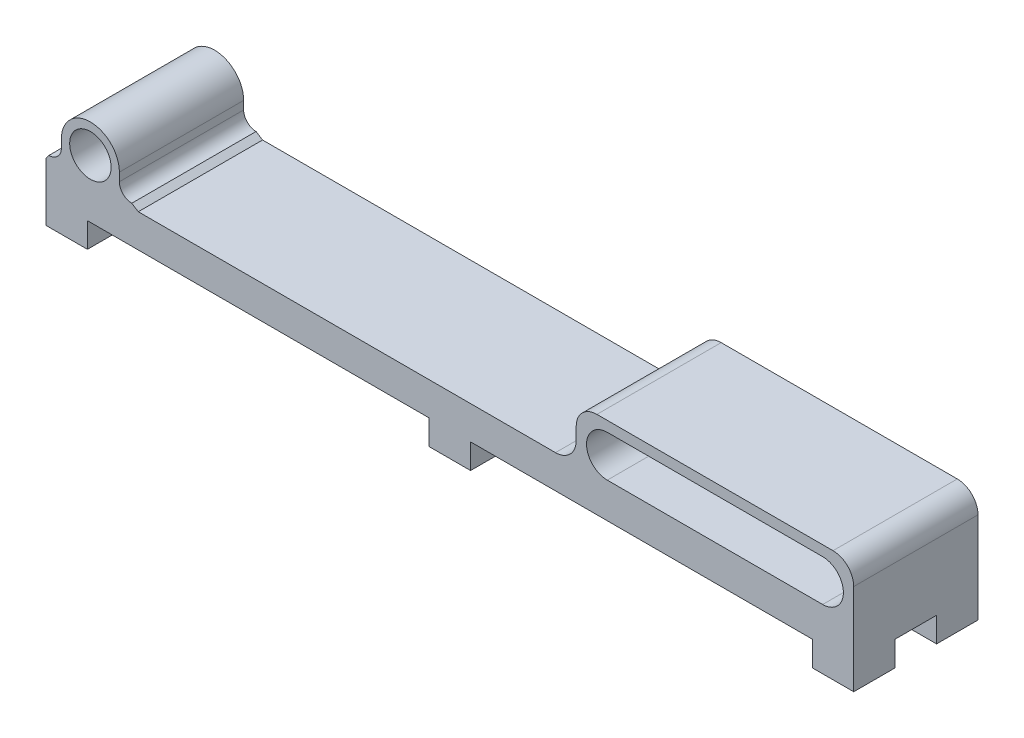
SolidWorks part; units mm, degrees
ref_plane "Front Plane" through (0, 0, 0) normal (0, 0, 1) x (1, 0, 0)
ref_plane "Top Plane" through (0, 0, 0) normal (0, 1, 0) x (1, 0, 0)
ref_plane "Right Plane" through (0, 0, 0) normal (1, 0, 0) x (0, 0, -1)
sketch "Sketch1" plane through (0, 0, 0) normal (0, 1, 0) x (1, 0, 0)
  line L1 (0, 0) -> (195, 0)
  line L2 (0, 0) -> (0, 30)
  line L3 (0, 30) -> (195, 30)
  line L4 (195, 0) -> (195, 30)
  dimension "D1" = 195
  dimension "D2" = 30
extrude "Boss-Extrude1" add sketch "Sketch1" along normal blind 8
sketch "Sketch2" plane through (0, 8, 0) normal (0, 1, 0) x (1, 0, 0)
  line L0 (195, 30) -> (0, 30) construction
  line L1 (4.7153, 30) -> (16.7153, 30)
  line L2 (4.7153, 30) -> (4.7153, 0)
  line L3 (4.7153, 0) -> (16.7153, 0)
  line L4 (16.7153, 30) -> (16.7153, 0)
  line L5 (0, 0) -> (195, 0) construction
  dimension "D1" = 12
extrude "Boss-Extrude2" add sketch "Sketch2" along normal blind 12
sketch "Sketch4" plane through (0, 0, -30) normal (0, 0, -1) x (-1, 0, 0)
  line L0 (-16.7153, 20) -> (-4.7153, 20) construction
  line L1 (-4.7153, 20) -> (-4.7153, 8) construction
  circle A0 centre (-10.7153, 14) radius 5
  dimension "D1" = 6
  dimension "D2" = 6
extrude "Cut-Extrude1" cut sketch "Sketch4" against normal through all
fillet "Fillet1" radius 4 2 edges at (4.7153, 8, -15) (16.7153, 8, -15)
fillet "Fillet2" radius 6 2 edges at (4.7153, 20, -15) (16.7153, 20, -15)
sketch "Sketch11" plane through (0, 0, -30) normal (0, 0, -1) x (-1, 0, 0)
  line L0 (-16.7153, 14) -> (-16.7153, 12) construction
  line L2 (-4.7153, 14) -> (-4.7153, 12) construction
  line L3 (-16.7153, 14) -> (-16.7153, 12)
  line L4 (-4.7153, 14) -> (-4.7153, 12)
  line L5 (-17.7153, 14) -> (-17.7153, 12)
  line L6 (-3.7153, 14) -> (-3.7153, 12)
  line L7 (-20.7153, 9) -> (-22.2788, 8)
  line L8 (-20.7153, 8) -> (-195, 8) construction
  line L9 (-22.2788, 8) -> (-20.7153, 8)
  line L10 (-0.7153, 9) -> (0, 8)
  line L11 (0, 8) -> (-0.7153, 8)
  arc A4 (-4.7153, 14) -> (-10.7153, 20) centre (-10.7153, 14) ccw construction
  arc A5 (-10.7153, 20) -> (-16.7153, 14) centre (-10.7153, 14) ccw construction
  arc A6 (-20.7153, 8) -> (-16.7153, 12) centre (-20.7153, 12) ccw construction
  arc A7 (-4.7153, 12) -> (-0.7153, 8) centre (-0.7153, 12) ccw construction
  arc A8 (-20.7153, 8) -> (-16.7153, 12) centre (-20.7153, 12) ccw
  arc A9 (-4.7153, 12) -> (-0.7153, 8) centre (-0.7153, 12) ccw
  arc A10 (-4.7153, 14) -> (-10.7153, 20) centre (-10.7153, 14) ccw
  arc A11 (-10.7153, 20) -> (-16.7153, 14) centre (-10.7153, 14) ccw
  arc A12 (-20.7153, 9) -> (-17.7153, 12) centre (-20.7153, 12) ccw
  arc A13 (-10.7153, 21) -> (-17.7153, 14) centre (-10.7153, 14) ccw
  arc A14 (-3.7153, 14) -> (-10.7153, 21) centre (-10.7153, 14) ccw
  arc A15 (-3.7153, 12) -> (-0.7153, 9) centre (-0.7153, 12) ccw
  dimension "D1" = 1
extrude "Boss-Extrude4" add sketch "Sketch11" against normal up to surface (30 mm away) up to face at (5.7153, 14, 0)
sketch "Sketch15" plane through (0, 8, 0) normal (0, 1, 0) x (1, 0, 0)
  line L0 (195, 15) -> (22.2788, 15) construction
  line L1 (195, 30) -> (128, 30)
  line L2 (195, 30) -> (195, 23)
  line L3 (195, 23) -> (128, 23)
  line L4 (128, 30) -> (128, 23)
  line L5 (195, 0) -> (195, 30) construction
  line L6 (22.2788, 0) -> (22.2788, 30) construction
  line L7 (195, 7) -> (128, 7)
  line L8 (128, 0) -> (128, 7)
  line L9 (195, 0) -> (128, 0)
  line L10 (195, 0) -> (195, 7)
  dimension "D1" = 7
  dimension "D2" = 67
extrude "Boss-Extrude6" add sketch "Sketch15" along normal blind 13
sketch "Sketch16" plane through (0, 0, -30) normal (0, 0, -1) x (-1, 0, 0)
  line L0 (-195, 21) -> (-195, 0) construction
  line L1 (-192.5, 18.5) -> (-130.5, 18.5)
  line L2 (-192.5, 18.5) -> (-192.5, 8.5)
  line L3 (-192.5, 8.5) -> (-130.5, 8.5)
  line L4 (-130.5, 18.5) -> (-130.5, 8.5)
  line L5 (-128, 21) -> (-128, 8) construction
  line L6 (-195, 21) -> (-128, 21) construction
  dimension "D1" = 2.5
  dimension "D2" = 2.5
  dimension "D3" = 10
  dimension "D4" = 2.5
extrude "Cut-Extrude4" cut sketch "Sketch16" against normal through all
fillet "Fillet5" radius 5 4 edges at (130.5, 18.5, -26.5) (130.5, 8.5, -26.5) (192.5, 18.5, -26.5) (192.5, 8.5, -26.5)
fillet "Fillet6" radius 5 2 edges at (195, 21, -26.5) (128, 21, -26.5)
fillet "Fillet7" radius 5 1 edges at (128, 8, -26.5)
sketch "Sketch17" plane through (0, 0, 0) normal (0, -1, 0) x (1, 0, 0)
  line L0 (0, 0) -> (195, 0) construction
  line L1 (92.5, 0) -> (102.5, 0)
  line L2 (92.5, 0) -> (92.5, -30)
  line L3 (92.5, -30) -> (102.5, -30)
  line L4 (102.5, 0) -> (102.5, -30)
  line L5 (195, -30) -> (0, -30) construction
  line L6 (0, -30) -> (0, 0) construction
  dimension "D1" = 10
  dimension "D2" = 92.5
extrude "Boss-Extrude7" add sketch "Sketch17" along normal blind 6
fillet "Fillet8" radius 5 6 edges at (195, 21, -3.5) (128, 21, -3.5) (192.5, 18.5, -3.5) (192.5, 8.5, -3.5) (130.5, 18.5, -3.5) (130.5, 8.5, -3.5)
fillet "Fillet9" radius 5 1 edges at (128, 8, -3.5)
sketch "Sketch20" plane through (0, 0, -23) normal (0, 0, 1) x (1, 0, 0)
  line L2 (135.5, 8.5) -> (187.5, 8.5)
  line L3 (187.5, 18.5) -> (135.5, 18.5)
  line L4 (135.5, 8.5) -> (187.5, 8.5)
  line L5 (187.5, 18.5) -> (135.5, 18.5)
  line L18 (195, 0) -> (195, 16)
  line L19 (190, 21) -> (133, 21)
  line L20 (128, 16) -> (128, 13)
  line L21 (123, 8) -> (22.2788, 8)
  line L22 (22.2788, 8) -> (20.7153, 9)
  line L23 (17.7153, 12) -> (17.7153, 14)
  line L24 (3.7153, 14) -> (3.7153, 12)
  line L25 (0.7153, 9) -> (0, 8)
  line L26 (0, 8) -> (0, 0)
  line L27 (0, 0) -> (92.5, 0)
  line L28 (92.5, 0) -> (92.5, -6)
  line L29 (92.5, -6) -> (102.5, -6)
  line L30 (102.5, -6) -> (102.5, 0)
  line L31 (102.5, 0) -> (195, 0)
  line L32 (195, 0) -> (195, 16)
  line L33 (190, 21) -> (133, 21)
  line L34 (128, 16) -> (128, 13)
  line L35 (123, 8) -> (22.2788, 8)
  line L36 (22.2788, 8) -> (20.7153, 9)
  line L37 (17.7153, 12) -> (17.7153, 14)
  line L38 (3.7153, 14) -> (3.7153, 12)
  line L39 (0.7153, 9) -> (0, 8)
  line L40 (0, 8) -> (0, 0)
  line L41 (0, 0) -> (92.5, 0)
  line L42 (92.5, 0) -> (92.5, -6)
  line L43 (92.5, -6) -> (102.5, -6)
  line L44 (102.5, -6) -> (102.5, 0)
  line L45 (102.5, 0) -> (195, 0)
  circle A1 centre (10.7153, 14) radius 5
  circle A2 centre (10.7153, 14) radius 5
  arc A6 (130.5, 13.5) -> (135.5, 8.5) centre (135.5, 13.5) ccw
  arc A7 (135.5, 18.5) -> (130.5, 13.5) centre (135.5, 13.5) ccw
  arc A8 (192.5, 13.5) -> (187.5, 18.5) centre (187.5, 13.5) ccw
  arc A9 (187.5, 8.5) -> (192.5, 13.5) centre (187.5, 13.5) ccw
  arc A10 (130.5, 13.5) -> (135.5, 8.5) centre (135.5, 13.5) ccw
  arc A11 (135.5, 18.5) -> (130.5, 13.5) centre (135.5, 13.5) ccw
  arc A12 (192.5, 13.5) -> (187.5, 18.5) centre (187.5, 13.5) ccw
  arc A13 (187.5, 8.5) -> (192.5, 13.5) centre (187.5, 13.5) ccw
  arc A16 (195, 16) -> (190, 21) centre (190, 16) ccw
  arc A17 (133, 21) -> (128, 16) centre (133, 16) ccw
  arc A18 (123, 8) -> (128, 13) centre (123, 13) ccw
  arc A19 (17.7153, 12) -> (20.7153, 9) centre (20.7153, 12) ccw
  arc A20 (17.7153, 14) -> (3.7153, 14) centre (10.7153, 14) ccw
  arc A21 (0.7153, 9) -> (3.7153, 12) centre (0.7153, 12) ccw
  arc A22 (195, 16) -> (190, 21) centre (190, 16) ccw
  arc A23 (133, 21) -> (128, 16) centre (133, 16) ccw
  arc A24 (123, 8) -> (128, 13) centre (123, 13) ccw
  arc A25 (17.7153, 12) -> (20.7153, 9) centre (20.7153, 12) ccw
  arc A26 (17.7153, 14) -> (3.7153, 14) centre (10.7153, 14) ccw
  arc A27 (0.7153, 9) -> (3.7153, 12) centre (0.7153, 12) ccw
  dimension "D1" = 0
  dimension "D2" = 0
  dimension "D3" = 0
extrude "Boss-Extrude8" add sketch "Sketch20" along normal up to surface (16 mm away) up to face at (161.5, 13.5, -7)
sketch "Sketch21" plane through (0, 0, 0) normal (0, -1, 0) x (-1, 0, 0)
  line L0 (-92.5, 30) -> (0, 30) construction
  line L1 (0, 0) -> (-10, 0)
  line L2 (0, 0) -> (0, 30)
  line L3 (0, 30) -> (-10, 30)
  line L4 (-10, 0) -> (-10, 30)
  line L5 (-195, 30) -> (-102.5, 30) construction
  line L7 (-195, 0) -> (-195, 30)
  line L8 (-195, 30) -> (-185, 30)
  line L9 (-185, 0) -> (-185, 30)
  line L10 (-195, 0) -> (-185, 0)
  dimension "D1" = 10
  dimension "D2" = 10
extrude "Boss-Extrude9" add sketch "Sketch21" along normal blind 6
sketch "Sketch22" plane through (0, -6, 0) normal (0, -1, 0) x (-1, 0, 0)
  line L0 (0, 0) -> (0, 30) construction
  line L1 (0, 10) -> (-10, 10)
  line L2 (0, 10) -> (0, 20)
  line L3 (0, 20) -> (-10, 20)
  line L4 (-10, 10) -> (-10, 20)
  line L5 (-10, 30) -> (-10, 0) construction
  line L6 (0, 30) -> (-10, 30) construction
  line L7 (-92.5, 0) -> (-92.5, 30) construction
  line L8 (-92.5, 10) -> (-102.5, 10)
  line L9 (-92.5, 10) -> (-92.5, 20)
  line L10 (-92.5, 20) -> (-102.5, 20)
  line L11 (-102.5, 10) -> (-102.5, 20)
  line L12 (-102.5, 30) -> (-102.5, 0) construction
  line L13 (-185, 0) -> (-185, 30) construction
  line L14 (-185, 10) -> (-195, 10)
  line L15 (-185, 10) -> (-185, 20)
  line L16 (-185, 20) -> (-195, 20)
  line L17 (-195, 10) -> (-195, 20)
  line L18 (-195, 30) -> (-195, 0) construction
  dimension "D1" = 10
  dimension "D2" = 10
extrude "Cut-Extrude5" cut sketch "Sketch22" against normal blind 6
equation "\"7.5o\"=7.56878"
